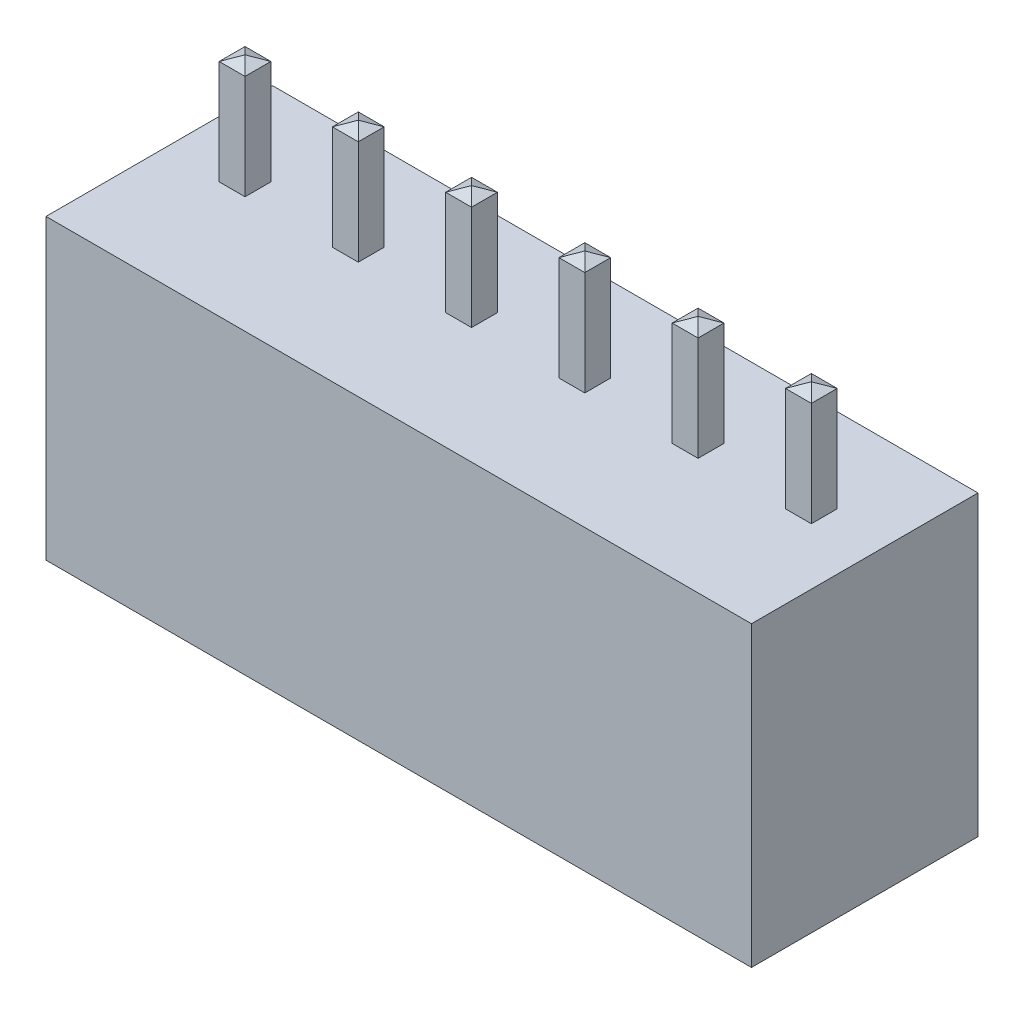
SolidWorks part; units mm, degrees
ref_plane "Спереди" through (0, 0, 0) normal (0, 0, 1) x (1, 0, 0)
ref_plane "Сверху" through (0, 0, 0) normal (0, 1, 0) x (1, 0, 0)
ref_plane "Справа" through (0, 0, 0) normal (1, 0, 0) x (0, 0, -1)
sketch "Эскиз1" plane through (0, 0, 0) normal (0, 0, 1) x (1, 0, 0)
  line L1 (10.9, 9.2) -> (-10.9, 9.2)
  line L2 (10.9, 9.2) -> (10.9, 0)
  line L3 (10.9, 0) -> (-10.9, 0)
  line L4 (-10.9, 9.2) -> (-10.9, 0)
  line L5 (10.9, 9.2) -> (-10.9, 0) construction
  line L6 (10.9, 0) -> (-10.9, 9.2) construction
  point P0 (0, 4.6)
  dimension "D1" = 9.2
  dimension "D2" = 21.8
extrude "Бобышка-Вытянуть1" add sketch "Эскиз1" along normal blind 7
sketch "Эскиз2" plane through (0, 9.2, 9.2) normal (0, -1, 0) x (-1, 0, 0)
  line L0 (10.9, 9.2) -> (-10.9, 9.2) construction
  line L1 (-9.15, 5.8) -> (-8.35, 5.8)
  line L2 (-9.15, 5.8) -> (-9.15, 6.6)
  line L3 (-9.15, 6.6) -> (-8.35, 6.6)
  line L4 (-8.35, 5.8) -> (-8.35, 6.6)
  line L5 (-9.15, 5.8) -> (-8.35, 6.6) construction
  line L6 (-9.15, 6.6) -> (-8.35, 5.8) construction
  line L8 (-10.9, 2.2) -> (-10.9, 9.2) construction
  point P0 (-8.75, 6.2)
  point P9 (0, 0)
  dimension "D1" = 3
  dimension "D2" = 0.8
  dimension "D3" = 2.15
extrude "Бобышка-Вытянуть2" add sketch "Эскиз2" against normal blind 3.4
chamfer "Фаска1" distance 0.4 angle 24 4 edges at (8.75, 12.6, 2.6) (8.35, 12.6, 3) (8.75, 12.6, 3.4) (9.15, 12.6, 3) first distance on face at (8.75, 12.6, 3)
sketch "Эскиз3" plane through (0, 0, 0) normal (0, -1, 0) x (1, 0, 0)
  line L1 (7.15, 0.8) -> (10.25, 0.8)
  line L2 (7.15, 0.8) -> (7.15, 5)
  line L4 (10.25, 0.8) -> (10.25, 5)
  line L5 (7.15, 0.8) -> (10.25, 5) construction
  line L6 (7.15, 5) -> (10.25, 0.8) construction
  line L7 (-10.9, 0) -> (10.9, 0) construction
  line L9 (10.9, 7) -> (10.9, 0) construction
  line L10 (-10.9, 7) -> (10.9, 7) construction
  line L11 (7.15, 6.5) -> (10.25, 6.5)
  line L12 (7.15, 5) -> (8.15, 5)
  line L13 (8.15, 5) -> (7.15, 6.5)
  line L14 (10.25, 5) -> (9.25, 5)
  line L15 (9.25, 5) -> (10.25, 6.5)
  point P0 (8.7, 2.9)
  point P5 (8.7, 6.5)
  dimension "D1" = 2.2
  dimension "D2" = 0.8
  dimension "D3" = 2
  dimension "D4" = 3.1
  dimension "D5" = 0.5
  dimension "D6" = 1
extrude "Вырез-Вытянуть1" cut sketch "Эскиз3" against normal blind 7
pattern_linear "Линейный массив1" count 6 spacing 3.5 along (-1, 0, 0) of "Бобышка-Вытянуть2", "Фаска1"
pattern_linear "Линейный массив2" count 6 spacing 3.5 along (-1, 0, 0) of "Вырез-Вытянуть1"
sketch "Эскиз4" plane through (0, 7, 0) normal (0, -1, 0) x (1, 0, 0)
  line L1 (8.35, 3.4) -> (9.15, 3.4)
  line L2 (8.35, 3.4) -> (8.35, 2.6)
  line L3 (8.35, 2.6) -> (9.15, 2.6)
  line L4 (9.15, 3.4) -> (9.15, 2.6)
  line L5 (8.35, 3.4) -> (9.15, 2.6) construction
  line L6 (8.35, 2.6) -> (9.15, 3.4) construction
  line L8 (-10.9, 0) -> (10.9, 0) construction
  line L9 (9.15, 2.6) -> (9.15, 3.4) construction
  line L10 (8.35, 3.4) -> (8.35, 2.6) construction
  point P0 (8.75, 3)
  dimension "D1" = 3
extrude "Бобышка-Вытянуть3" add sketch "Эскиз4" along normal blind 6
chamfer "Фаска2" distance 0.4 angle 24 4 edges at (9.15, 1, 3) (8.75, 1, 3.4) (8.35, 1, 3) (8.75, 1, 2.6) first distance on face at (9.15, 4, 3) first distance on face at (8.75, 4, 3.4) first distance on face at (8.35, 4, 3) first distance on face at (8.75, 4, 2.6)
pattern_linear "Линейный массив3" count 6 spacing 3.5 along (-1, 0, 0) of "Фаска2", "Бобышка-Вытянуть3"
equation "\"n\" = 6"
equation "\"width\"= 3.5 * ( \"n\" - 1 ) + 4.3"
equation "\"D2@Эскиз1\" = 3.5 * ( \"n\" - 1 ) + 4.3"
equation "\"D1@Линейный массив1\"=\"n\""
equation "\"D1@Линейный массив2\"=\"n\""
equation "\"D1@Линейный массив3\"=\"n\""
